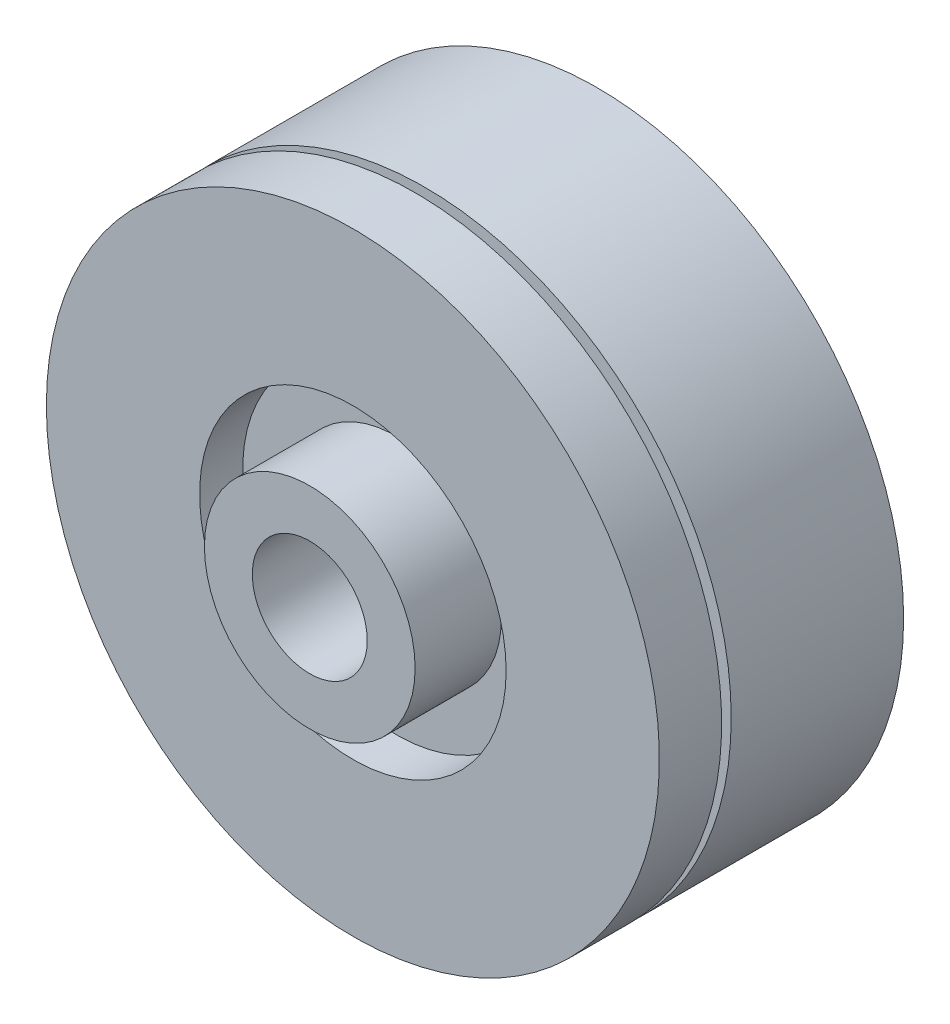
SolidWorks part; units mm, degrees
ref_plane "前视基准面" through (0, 0, 0) normal (0, 0, 1) x (1, 0, 0)
ref_plane "上视基准面" through (0, 0, 0) normal (0, 1, 0) x (1, 0, 0)
ref_plane "右视基准面" through (0, 0, 0) normal (1, 0, 0) x (0, 0, -1)
sketch "草图1" plane through (0, 0, 0) normal (0, 0, 1) x (1, 0, 0)
  circle A0 centre (0, 0) radius 16
extrude "凸台-拉伸1" add sketch "草图1" along normal blind 9
sketch "草图2" plane through (0, 0, 9) normal (0, 0, 1) x (1, 0, 0)
  circle A0 centre (0, 0) radius 6
extrude "凸台-拉伸2" add sketch "草图2" along normal blind 0.5
sketch "草图3" plane through (0, 0, 9.5) normal (0, 0, 1) x (1, 0, 0)
  circle A0 centre (0, 0) radius 16
extrude "凸台-拉伸3" add sketch "草图3" along normal blind 3.25
sketch "草图4" plane through (0, 0, 12.75) normal (0, 0, 1) x (1, 0, 0)
  circle A0 centre (0, 0) radius 5.5
extrude "凸台-拉伸4" add sketch "草图4" along normal blind 2.25
sketch "草图5" plane through (0, 0, 15) normal (0, 0, 1) x (1, 0, 0)
  circle A0 centre (0, 0) radius 3
extrude "切除-拉伸1" cut sketch "草图5" against normal blind 26.25
sketch "草图6" plane through (0, 0, 12.75) normal (0, 0, 1) x (1, 0, 0)
  circle A0 centre (0, 0) radius 5.5
  circle A1 centre (0, 0) radius 8
extrude "切除-拉伸2" cut sketch "草图6" against normal blind 2.25
sketch "草图7" plane through (0, 0, 0) normal (0, 0, -1) x (-1, 0, 0)
  circle A1 centre (8.6603, 5) radius 1
  circle A2 centre (-8.6603, 5) radius 1
  circle A3 centre (0, -10) radius 1
extrude "切除-拉伸3" cut sketch "草图7" against normal blind 6
